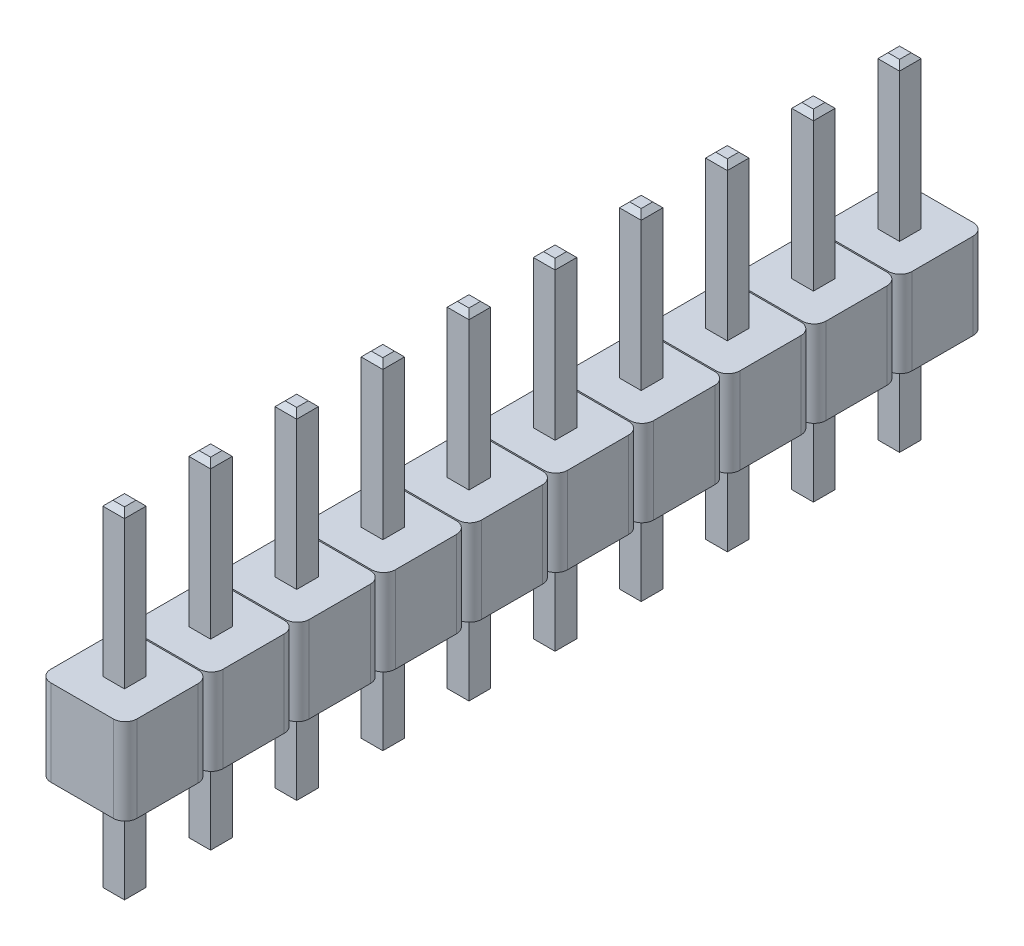
SolidWorks part; units mm, degrees
ref_plane "Front Plane" through (0, 0, 0) normal (0, 0, 1) x (1, 0, 0)
ref_plane "Top Plane" through (0, 0, 0) normal (0, 1, 0) x (1, 0, 0)
ref_plane "Right Plane" through (0, 0, 0) normal (1, 0, 0) x (0, 0, -1)
sketch "Sketch1" plane through (0, 0, 0) normal (0, 1, 0) x (1, 0, 0)
  line L1 (0, 0) -> (0.64, 0)
  line L2 (0, 0) -> (0, 0.64)
  line L3 (0, 0.64) -> (0.64, 0.64)
  line L4 (0.64, 0) -> (0.64, 0.64)
  dimension "D1" = 0.64
  dimension "D2" = 0.64
extrude "Boss-Extrude1" add sketch "Sketch1" along normal blind 10.04
chamfer "Chamfer1" distance 0.15 angle 45 8 edges at (0.32, 0, 0) (0.64, 0, -0.32) (0.32, 0, -0.64) (0, 0, -0.32) (0.32, 10.04, -0.64) (0.64, 10.04, -0.32) (0.32, 10.04, 0) (0, 10.04, -0.32)
ref_plane "Plane1" through (0, 5.54, 0) normal (0, 1, 0) x (1, 0, 0)
sketch "Sketch3" plane through (0, 5.54, 0) normal (0, 1, 0) x (1, 0, 0)
  line L0 (0.32, 0.64) -> (0.32, 0) construction
  line L1 (0, 0.64) -> (0.64, 0.64) construction
  line L2 (0.64, 0) -> (0, 0) construction
  line L4 (-0.6, -0.93) -> (1.24, -0.93)
  line L5 (-0.95, -0.58) -> (-0.95, 1.22)
  line L6 (-0.6, 1.57) -> (1.24, 1.57)
  line L7 (1.59, -0.58) -> (1.59, 1.22)
  line L8 (-0.95, -0.93) -> (1.59, 1.57) construction
  line L9 (-0.95, 1.57) -> (1.59, -0.93) construction
  arc A0 (-0.6, -0.93) -> (-0.95, -0.58) centre (-0.6, -0.58) cw
  arc A1 (1.24, 1.57) -> (1.59, 1.22) centre (1.24, 1.22) cw
  arc A2 (-0.95, 1.22) -> (-0.6, 1.57) centre (-0.6, 1.22) cw
  arc A3 (1.24, -0.93) -> (1.59, -0.58) centre (1.24, -0.58) ccw
  point P6 (0.32, 0.32)
  point P7 (0.32, 0.32)
  dimension "D3" = 0.35
  dimension "D1" = 2.5
  dimension "D2" = 2.54
extrude "Boss-Extrude2" add sketch "Sketch3" against normal blind 2.54
ref_axis "Axis1" through (0.32, 3, 0.93) along (0, 0, -1)
pattern_linear "LPattern2" count 10 spacing 2.54 along (0, 0, -1) of bodies 102
